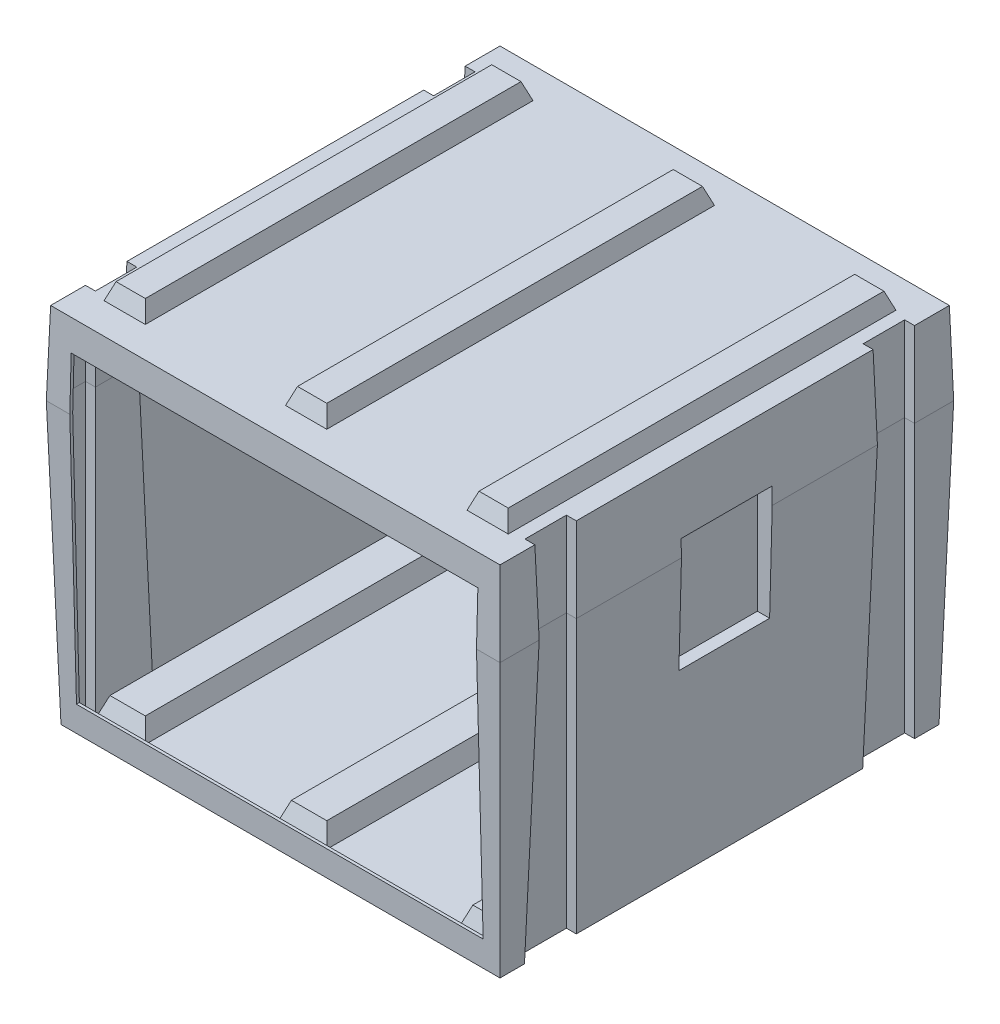
SolidWorks part; units mm, degrees
ref_plane "Front Plane" through (0, 0, 0) normal (0, 0, 1) x (1, 0, 0)
ref_plane "Top Plane" through (0, 0, 0) normal (0, 1, 0) x (1, 0, 0)
ref_plane "Right Plane" through (0, 0, 0) normal (1, 0, 0) x (0, 0, -1)
ref_plane "Plane1" through (0, 340, 0) normal (0, 1, 0) x (1, 0, 0)
sketch "Sketch1" plane through (0, 340, 0) normal (0, 1, 0) x (1, 0, 0)
  line L0 (-275, 275) -> (275, 275)
  line L1 (275, 275) -> (275, 227.5)
  line L2 (275, 227.5) -> (263, 227.5)
  line L3 (263, 227.5) -> (263, 182.5)
  line L4 (263, 182.5) -> (275, 182.5)
  line L5 (275, 182.5) -> (275, -182.5)
  line L6 (275, -182.5) -> (263, -182.5)
  line L7 (263, -182.5) -> (263, -227.5)
  line L8 (263, -227.5) -> (275, -227.5)
  line L9 (275, -227.5) -> (275, -275)
  line L10 (275, -275) -> (-275, -275)
  line L11 (-275, -275) -> (-275, -227.5)
  line L12 (-275, -227.5) -> (-263, -227.5)
  line L13 (-263, -227.5) -> (-263, -182.5)
  line L14 (-263, -182.5) -> (-275, -182.5)
  line L15 (-275, -182.5) -> (-275, 182.5)
  line L16 (-275, 182.5) -> (-263, 182.5)
  line L17 (-263, 182.5) -> (-263, 227.5)
  line L18 (-263, 227.5) -> (-275, 227.5)
  line L19 (-275, 227.5) -> (-275, 275)
extrude "Boss-Extrude1" add sketch "Sketch1" along normal blind 100 draft 1.5
sketch "Sketch2" plane through (0, 340, 0) normal (0, 1, 0) x (1, 0, 0)
  line L0 (-275, 275) -> (275, 275)
  line L1 (275, 275) -> (275, 227.5)
  line L2 (275, 227.5) -> (263, 227.5)
  line L3 (263, 227.5) -> (263, 182.5)
  line L4 (263, 182.5) -> (275, 182.5)
  line L5 (275, 182.5) -> (275, -182.5)
  line L6 (275, -182.5) -> (263, -182.5)
  line L7 (263, -182.5) -> (263, -227.5)
  line L8 (263, -227.5) -> (275, -227.5)
  line L9 (275, -227.5) -> (275, -275)
  line L10 (275, -275) -> (-275, -275)
  line L11 (-275, -275) -> (-275, -227.5)
  line L12 (-275, -227.5) -> (-263, -227.5)
  line L13 (-263, -227.5) -> (-263, -182.5)
  line L14 (-263, -182.5) -> (-275, -182.5)
  line L15 (-275, -182.5) -> (-275, 182.5)
  line L16 (-275, 182.5) -> (-263, 182.5)
  line L17 (-263, 182.5) -> (-263, 227.5)
  line L18 (-263, 227.5) -> (-275, 227.5)
  line L19 (-275, 227.5) -> (-275, 275)
extrude "Boss-Extrude2" add sketch "Sketch2" against normal blind 340 draft 1.5
ref_plane "Plane2" through (0, 440, 0) normal (0, 1, 0) x (1, 0, 0)
sketch "Sketch3" plane through (0, 440, 0) normal (0, 1, 0) x (1, 0, 0)
  line L0 (-245, 235) -> (-195, 235)
  line L1 (-195, 235) -> (-195, -235)
  line L2 (-195, -235) -> (-245, -235)
  line L3 (-245, -235) -> (-245, 235)
  line L4 (-25, 235) -> (25, 235)
  line L5 (25, 235) -> (25, -235)
  line L6 (25, -235) -> (-25, -235)
  line L7 (-25, -235) -> (-25, 235)
  line L8 (195, 235) -> (245, 235)
  line L9 (245, 235) -> (245, -235)
  line L10 (245, -235) -> (195, -235)
  line L11 (195, -235) -> (195, 235)
  dimension "D1" = 50
  dimension "D2" = 470
extrude "Boss-Extrude3" add sketch "Sketch3" along normal blind 20 draft 20
sketch "Sketch4" plane through (0, 0, 0) normal (0, 1, 0) x (1, 0, 0)
  line L0 (-247, 237) -> (-193, 237)
  line L1 (-193, 237) -> (-193, -237)
  line L2 (-193, -237) -> (-247, -237)
  line L3 (-247, -237) -> (-247, 237)
  line L4 (-27, 237) -> (27, 237)
  line L5 (27, 237) -> (27, -237)
  line L6 (27, -237) -> (-27, -237)
  line L7 (-27, -237) -> (-27, 237)
  line L8 (193, 237) -> (247, 237)
  line L9 (247, 237) -> (247, -237)
  line L10 (247, -237) -> (193, -237)
  line L11 (193, -237) -> (193, 237)
extrude "Cut-Extrude1" cut sketch "Sketch4" along normal blind 22 draft 20
ref_plane "Plane3" through (275, 0, 0) normal (1, 0, 0) x (0, 0, -1)
sketch "Sketch5" plane through (275, 0, 0) normal (1, 0, 0) x (0, 0, -1)
  line L0 (55, 220) -> (55, 360)
  line L1 (55, 360) -> (-55, 360)
  line L2 (-55, 360) -> (-55, 220)
  line L3 (-55, 220) -> (55, 220)
  line L4 (275, 0) -> (275, 440) construction
  line L5 (275, 440) -> (-275, 440) construction
  line L6 (-275, 440) -> (-275, 0) construction
  line L7 (-275, 0) -> (275, 0) construction
  dimension "D1" = 140
  dimension "D2" = 110
  dimension "D3" = 550
extrude "Cut-Extrude2" cut sketch "Sketch5" against normal mid plane 36
ref_plane "Plane4" through (-275, 0, 0) normal (1, 0, 0) x (0, 0, -1)
sketch "Sketch6" plane through (-275, 0, 0) normal (1, 0, 0) x (0, 0, -1)
  line L0 (55, 220) -> (55, 360)
  line L1 (55, 360) -> (-55, 360)
  line L2 (-55, 360) -> (-55, 220)
  line L3 (-55, 220) -> (55, 220)
extrude "Cut-Extrude3" cut sketch "Sketch6" against normal mid plane 36
shell "Shell1" thickness 3.5
ref_plane "Plane5" through (0, 0, 275) normal (0, 0, 1) x (1, 0, 0)
sketch "Sketch7" plane through (0, 0, 275) normal (0, 0, 1) x (1, 0, 0)
  line L0 (-246.5, 31.5) -> (246.5, 31.5)
  line L1 (246.5, 31.5) -> (246.5, 403.5)
  line L2 (246.5, 403.5) -> (-246.5, 403.5)
  line L3 (-246.5, 403.5) -> (-246.5, 31.5)
  line L4 (-275, 0) -> (275, 0) construction
  line L5 (275, 0) -> (275, 440) construction
  line L6 (275, 440) -> (-275, 440) construction
  line L7 (-275, 440) -> (-275, 0) construction
  dimension "D1" = 493
  dimension "D2" = 372
  dimension "D3" = 550
  dimension "D4" = 440
extrude "Cut-Extrude4" cut sketch "Sketch7" against normal mid plane 34.8064
ref_plane "Plane6" through (0, 0, 258.4865) normal (0, 0, 1) x (1, 0, 0)
sketch "Sketch8" plane through (0, 0, 258.4865) normal (0, 0, 1) x (1, 0, 0)
  line L0 (-271.9731, 428.5) -> (271.9731, 428.5)
  line L1 (271.9731, 428.5) -> (271.9731, 437.5)
  line L2 (271.9731, 437.5) -> (-271.9731, 437.5)
  line L3 (-271.9731, 437.5) -> (-271.9731, 428.5)
extrude "Boss-Extrude4" add sketch "Sketch8" along normal mid plane 26.9731
